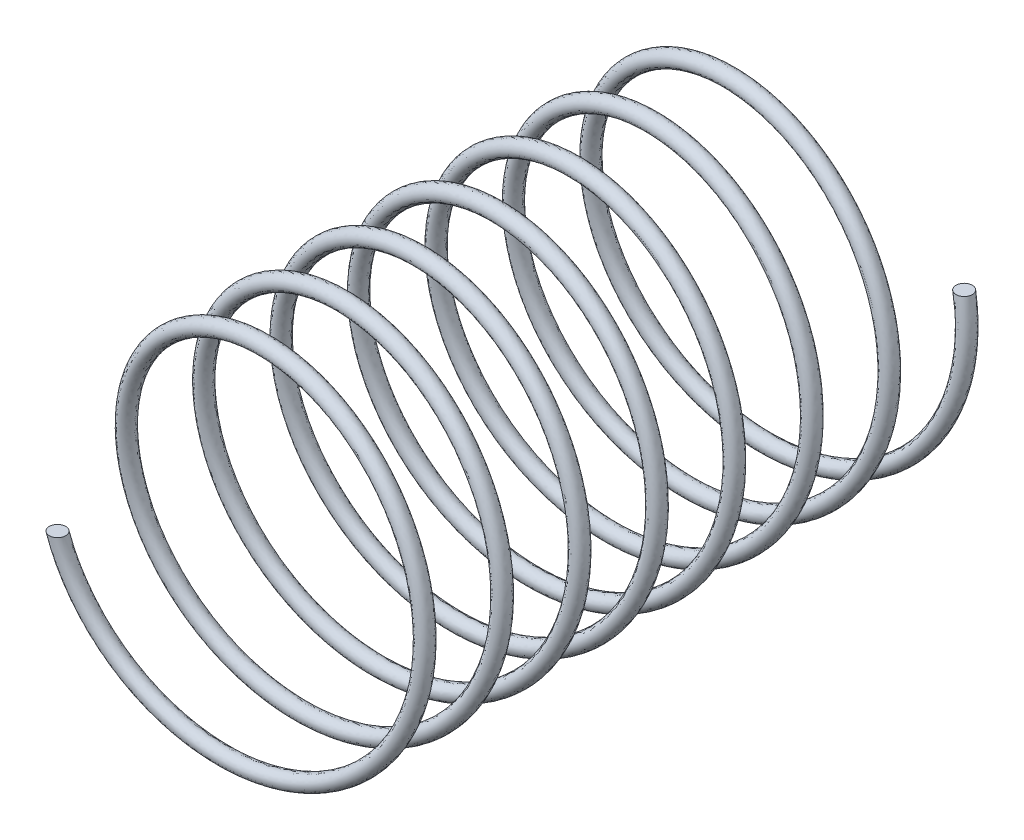
SolidWorks part; units mm, degrees
ref_plane "Front Plane" through (0, 0, 0) normal (0, 0, 1) x (1, 0, 0)
ref_plane "Top Plane" through (0, 0, 0) normal (0, 1, 0) x (1, 0, 0)
ref_plane "Right Plane" through (0, 0, 0) normal (1, 0, 0) x (0, 0, -1)
sketch "Sketch1" plane through (0, 0, 0) normal (0, 0, 1) x (1, 0, 0)
  circle A0 centre (0, 0) radius 40
curve "Helix/Spiral1" pitch 19 height 142.5 turns 7.5
ref_plane "Plane1" through (0, 10, 0) normal (0, 1, 0) x (1, 0, 0)
sketch "Sketch2" plane through (0, 10, 0) normal (0, 1, 0) x (1, 0, 0)
  circle A0 centre (40, 0) radius 2
  spline S0 degree 3 poles (40, 0) (40, -0.2257) (39.3258, -0.6788) (36.3425, -1.3571) (31.5368, -2.0357) (25.1498, -2.7143) (17.5016, -3.3929) (6.1339, -4.2976) (-6.1339, -5.2024) (-17.5016, -6.1071) (-25.1498, -6.7857) (-31.5368, -7.4643) (-36.3425, -8.1429) (-39.3258, -8.8214) (-40.3371, -9.5) (-39.3258, -10.1786) (-36.3425, -10.8571) (-31.5368, -11.5357) (-25.1498, -12.2143) (-17.5016, -12.8929) (-6.1339, -13.7976) (6.1339, -14.7024) (17.5016, -15.6071) (25.1498, -16.2857) (31.5368, -16.9643) (36.3425, -17.6429) (39.3258, -18.3214) (40.3371, -19) (39.3258, -19.6786) (36.3425, -20.3571) (31.5368, -21.0357) (25.1498, -21.7143) (17.5016, -22.3929) (6.1339, -23.2976) (-6.1339, -24.2024) (-17.5016, -25.1071) (-25.1498, -25.7857) (-31.5368, -26.4643) (-36.3425, -27.1429) (-39.3258, -27.8214) (-40.3371, -28.5) (-39.3258, -29.1786) (-36.3425, -29.8571) (-31.5368, -30.5357) (-25.1498, -31.2143) (-17.5016, -31.8929) (-6.1339, -32.7976) (6.1339, -33.7024) (17.5016, -34.6071) (25.1498, -35.2857) (31.5368, -35.9643) (36.3425, -36.6429) (39.3258, -37.3214) (40.3371, -38) (39.3258, -38.6786) (36.3425, -39.3571) (31.5368, -40.0357) (25.1498, -40.7143) (17.5016, -41.3929) (6.1339, -42.2976) (-6.1339, -43.2024) (-17.5016, -44.1071) (-25.1498, -44.7857) (-31.5368, -45.4643) (-36.3425, -46.1429) (-39.3258, -46.8214) (-40.3371, -47.5) (-39.3258, -48.1786) (-36.3425, -48.8571) (-31.5368, -49.5357) (-25.1498, -50.2143) (-17.5016, -50.8929) (-6.1339, -51.7976) (6.1339, -52.7024) (17.5016, -53.6071) (25.1498, -54.2857) (31.5368, -54.9643) (36.3425, -55.6429) (39.3258, -56.3214) (40.3371, -57) (39.3258, -57.6786) (36.3425, -58.3571) (31.5368, -59.0357) (25.1498, -59.7143) (17.5016, -60.3929) (6.1339, -61.2976) (-6.1339, -62.2024) (-17.5016, -63.1071) (-25.1498, -63.7857) (-31.5368, -64.4643) (-36.3425, -65.1429) (-39.3258, -65.8214) (-40.3371, -66.5) (-39.3258, -67.1786) (-36.3425, -67.8571) (-31.5368, -68.5357) (-25.1498, -69.2143) (-17.5016, -69.8929) (-6.1339, -70.7976) (6.1339, -71.7024) (17.5016, -72.6071) (25.1498, -73.2857) (31.5368, -73.9643) (36.3425, -74.6429) (39.3258, -75.3214) (40.3371, -76) (39.3258, -76.6786) (36.3425, -77.3571) (31.5368, -78.0357) (25.1498, -78.7143) (17.5016, -79.3929) (6.1339, -80.2976) (-6.1339, -81.2024) (-17.5016, -82.1071) (-25.1498, -82.7857) (-31.5368, -83.4643) (-36.3425, -84.1429) (-39.3258, -84.8214) (-40.3371, -85.5) (-39.3258, -86.1786) (-36.3425, -86.8571) (-31.5368, -87.5357) (-25.1498, -88.2143) (-17.5016, -88.8929) (-6.1339, -89.7976) (6.1339, -90.7024) (17.5016, -91.6071) (25.1498, -92.2857) (31.5368, -92.9643) (36.3425, -93.6429) (39.3258, -94.3214) (40.3371, -95) (39.3258, -95.6786) (36.3425, -96.3571) (31.5368, -97.0357) (25.1498, -97.7143) (17.5016, -98.3929) (6.1339, -99.2976) (-6.1339, -100.2024) (-17.5016, -101.1071) (-25.1498, -101.7857) (-31.5368, -102.4643) (-36.3425, -103.1429) (-39.3258, -103.8214) (-40.3371, -104.5) (-39.3258, -105.1786) (-36.3425, -105.8571) (-31.5368, -106.5357) (-25.1498, -107.2143) (-17.5016, -107.8929) (-6.1339, -108.7976) (6.1339, -109.7024) (17.5016, -110.6071) (25.1498, -111.2857) (31.5368, -111.9643) (36.3425, -112.6429) (39.3258, -113.3214) (40.3371, -114) (39.3258, -114.6786) (36.3425, -115.3571) (31.5368, -116.0357) (25.1498, -116.7143) (17.5016, -117.3929) (6.1339, -118.2976) (-6.1339, -119.2024) (-17.5016, -120.1071) (-25.1498, -120.7857) (-31.5368, -121.4643) (-36.3425, -122.1429) (-39.3258, -122.8214) (-40.3371, -123.5) (-39.3258, -124.1786) (-36.3425, -124.8571) (-31.5368, -125.5357) (-25.1498, -126.2143) (-17.5016, -126.8929) (-6.1339, -127.7976) (6.1339, -128.7024) (17.5016, -129.6071) (25.1498, -130.2857) (31.5368, -130.9643) (36.3425, -131.6429) (39.3258, -132.3214) (40.3371, -133) (39.3258, -133.6786) (36.3425, -134.3571) (31.5368, -135.0357) (25.1498, -135.7143) (17.5016, -136.3929) (6.1339, -137.2976) (-6.1339, -138.2024) (-17.5016, -139.1071) (-25.1498, -139.7857) (-31.5368, -140.4643) (-36.3425, -141.1429) (-39.3258, -141.8212) (-40, -142.2743) (-40, -142.5) knots 0 0 0 0 0.004762 0.009524 0.014286 0.019048 0.02381 0.028571 0.038095 0.042857 0.047619 0.052381 0.057143 0.061905 0.066667 0.071429 0.07619 0.080952 0.085714 0.090476 0.095238 0.104762 0.109524 0.114286 0.119048 0.12381 0.128571 0.133333 0.138095 0.142857 0.147619 0.152381 0.157143 0.161905 0.171429 0.17619 0.180952 0.185714 0.190476 0.195238 0.2 0.204762 0.209524 0.214286 0.219048 0.22381 0.228571 0.238095 0.242857 0.247619 0.252381 0.257143 0.261905 0.266667 0.271429 0.27619 0.280952 0.285714 0.290476 0.295238 0.304762 0.309524 0.314286 0.319048 0.32381 0.328571 0.333333 0.338095 0.342857 0.347619 0.352381 0.357143 0.361905 0.371429 0.37619 0.380952 0.385714 0.390476 0.395238 0.4 0.404762 0.409524 0.414286 0.419048 0.42381 0.428571 0.438095 0.442857 0.447619 0.452381 0.457143 0.461905 0.466667 0.471429 0.47619 0.480952 0.485714 0.490476 0.495238 0.504762 0.509524 0.514286 0.519048 0.52381 0.528571 0.533333 0.538095 0.542857 0.547619 0.552381 0.557143 0.561905 0.571429 0.57619 0.580952 0.585714 0.590476 0.595238 0.6 0.604762 0.609524 0.614286 0.619048 0.62381 0.628571 0.638095 0.642857 0.647619 0.652381 0.657143 0.661905 0.666667 0.671429 0.67619 0.680952 0.685714 0.690476 0.695238 0.704762 0.709524 0.714286 0.719048 0.72381 0.728571 0.733333 0.738095 0.742857 0.747619 0.752381 0.757143 0.761905 0.771429 0.77619 0.780952 0.785714 0.790476 0.795238 0.8 0.804762 0.809524 0.814286 0.819048 0.82381 0.828571 0.838095 0.842857 0.847619 0.852381 0.857143 0.861905 0.866667 0.871429 0.87619 0.880952 0.885714 0.890476 0.895238 0.904762 0.909524 0.914286 0.919048 0.92381 0.928571 0.933333 0.938095 0.942857 0.947619 0.952381 0.957143 0.961905 0.971429 0.97619 0.980952 0.985714 0.990476 0.995238 1 1 1 1 construction
sweep "Sweep1" add profiles "Sketch2" path "Helix/Spiral1"
